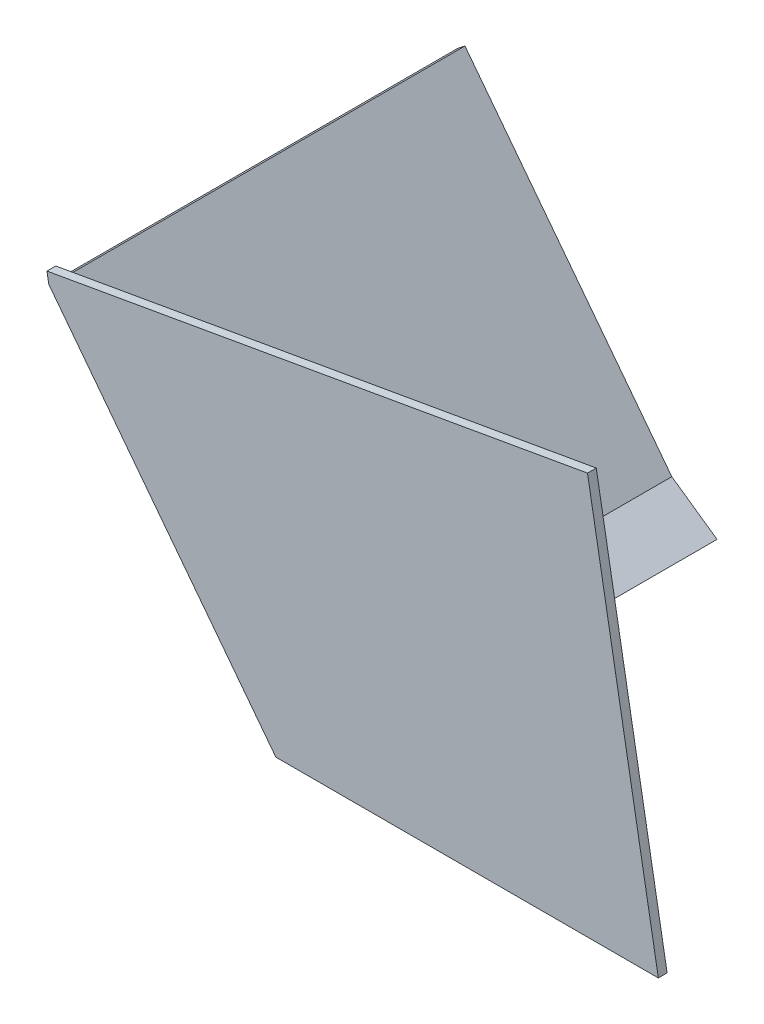
SolidWorks part; units mm, degrees
ref_plane "Front Plane" through (0, 0, 0) normal (0, 0, 1) x (1, 0, 0)
ref_plane "Top Plane" through (0, 0, 0) normal (0, 1, 0) x (1, 0, 0)
ref_plane "Right Plane" through (0, 0, 0) normal (1, 0, 0) x (0, 0, -1)
ref_axis "Axis1" through (0, 0, -14.8175) along (0, 0, 1)
sketch "Sketch1" plane through (0, 0, 0) normal (0, 0, 1) x (1, 0, 0)
  line L0 (-145.0806, 0) -> (145.0806, 0) construction
  line L1 (-162.6855, 22.9431) -> (-312.49, 218.1722)
  line L4 (-153.0846, 0) -> (-317.5278, 214.3065)
  line L5 (-317.5278, 214.3065) -> (-312.49, 218.1722)
  line L9 (-129.9194, 0) -> (-162.6855, 22.9431)
  line L10 (-129.9194, 0) -> (-153.0846, 0)
  line L11 (-162.6855, 22.9431) -> (-145.0806, 0) construction
  point P4 (0, 0)
  dimension "D1" = 52.5
  dimension "D2" = 35
  dimension "D3" = 275
  dimension "D4" = 275
  dimension "D5" = 40
  dimension "D6" = 6.35
extrude "Boss-Extrude1" add sketch "Sketch1" along normal blind 290
sketch "Sketch2" plane through (0, 0, 290) normal (0, 0, 1) x (1, 0, 0)
  line L0 (-153.0846, 0) -> (-317.5278, 214.3065)
  line L1 (-318.8842, 221.999) -> (72.5993, 291.0281)
  line L3 (123.9154, 0) -> (-153.0846, 0)
  line L4 (-317.5278, 214.3065) -> (-153.0846, 0) construction
  line L7 (-317.5278, 214.3065) -> (-318.8842, 221.999)
  line L8 (-312.49, 218.1722) -> (-317.5278, 214.3065) construction
  line L9 (55, 0) -> (-55, 0) construction
  line L10 (123.9154, 0) -> (72.5993, 291.0281)
  line L11 (-153.0846, 0) -> (-129.9194, 0) construction
  dimension "D1" = 10
  dimension "D2" = 274
  dimension "D3" = 277
extrude "Boss-Extrude2" add sketch "Sketch2" along normal blind 6.35
ref_plane "Plane1" through (0, 0, 0) normal (0.9848, 0.1736, 0) x (0, 0, 1)
